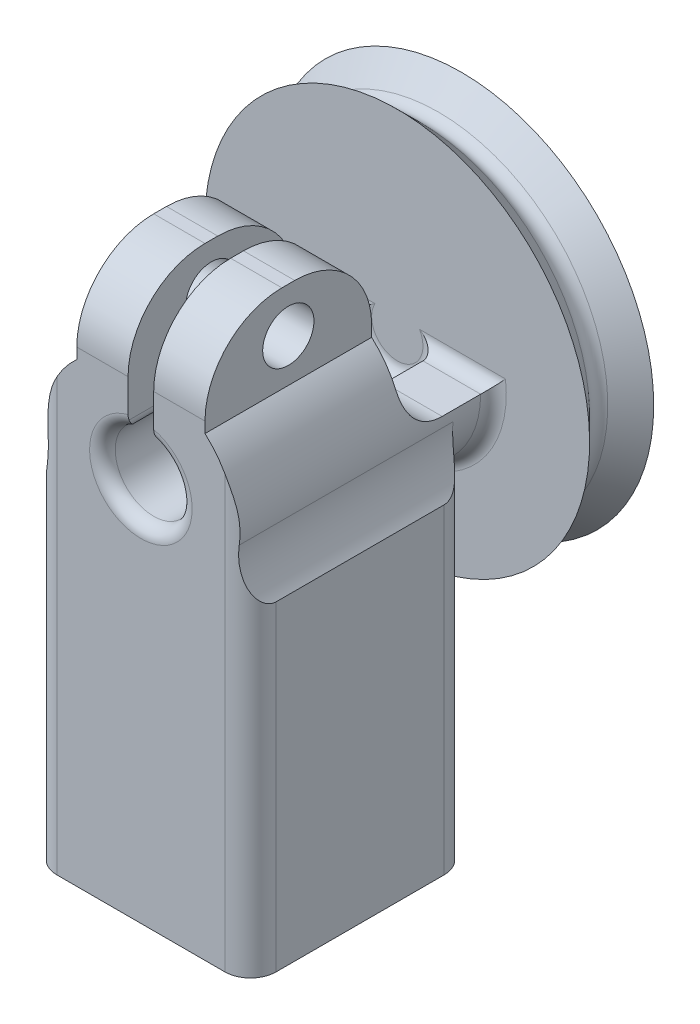
SolidWorks part; units mm, degrees
material "ABS PC"
ref_plane "Front Plane" through (0, 0, 0) normal (0, 0, 1) x (1, 0, 0)
ref_plane "Top Plane" through (0, 0, 0) normal (0, 1, 0) x (1, 0, 0)
ref_plane "Right Plane" through (0, 0, 0) normal (1, 0, 0) x (0, 0, -1)
sketch "Sketch1" plane through (0, 0, 0) normal (0, 0, 1) x (1, 0, 0)
  line L0 (-1, 7.433) -> (-1, 12.433)
  line L1 (-1, 12.433) -> (-5, 12.433)
  line L2 (-1, 2.8284) -> (-1, 7.433)
  line L3 (-5, 12.433) -> (-5, 5.5902)
  line L4 (1, 2.8284) -> (1, 7.433)
  line L5 (1, 7.433) -> (1, 12.433)
  line L6 (1, 12.433) -> (5, 12.433)
  line L7 (5, 12.433) -> (5, 5.5902)
  arc A0 (-5, 5.5902) -> (5, 5.5902) centre (0, 0) ccw
  arc A1 (-1, 2.8284) -> (1, 2.8284) centre (0, 0) ccw
  point P4 (0, 3)
  dimension "D1" = 6
  dimension "D2" = 15
  dimension "D3" = 5
  dimension "D4" = 5
  dimension "D5" = 4
  dimension "D6" = 4
extrude "Boss-Extrude1" add sketch "Sketch1" along normal blind 13
fillet "Fillet1" radius 1 3 edges at (0, -3, 13) (1, 2.8284, 6.5) (-1, 2.8284, 6.5)
fillet "Fillet2" radius 6 4 edges at (-3, 12.433, 0) (3, 12.433, 0) (3, 12.433, 13) (-3, 12.433, 13)
sketch "Sketch2" plane through (0, 0, 0) normal (0, 0, -1) x (-1, 0, 0)
  line L0 (-7.5, 0) -> (-3, 0)
  line L1 (3, 0) -> (7.5, 0)
  arc A0 (-7.5, 0) -> (7.5, 0) centre (0, 0) ccw
  arc A1 (-3, 0) -> (3, 0) centre (0, 0) ccw
extrude "Boss-Extrude2" add sketch "Sketch2" along normal blind 7
sketch "Sketch3" plane through (0, 0, 13) normal (0, 0, 1) x (1, 0, 0)
  line L1 (-8.55, -10) -> (8.55, -10)
  line L2 (-8.55, -10) -> (-8.55, -5)
  line L3 (-8.55, -5) -> (8.55, -5)
  line L4 (8.55, -10) -> (8.55, -5)
  line L5 (-8.55, -10) -> (8.55, -5) construction
  line L6 (-8.55, -5) -> (8.55, -10) construction
  arc A0 (-5, 5.5902) -> (5, 5.5902) centre (0, 0) ccw construction
  point P0 (0, -7.5)
  dimension "D1" = 17.1
  dimension "D2" = 5
extrude "Boss-Extrude3" add sketch "Sketch3" against normal blind 17.1
fillet "Fillet3" radius 6 2 edges at (5.5902, -5, 4.45) (-5.5902, -5, 4.45)
sketch "Sketch4" plane through (0, -10, 0) normal (0, -1, 0) x (1, 0, 0)
  line L4 (8.55, 13) -> (-8.55, 13)
  line L5 (-8.55, 13) -> (-8.55, -4.1)
  line L6 (-8.55, -4.1) -> (8.55, -4.1)
  line L7 (8.55, -4.1) -> (8.55, 13)
  line L8 (8.55, 13) -> (-8.55, 13)
  line L9 (-8.55, 13) -> (-8.55, -4.1)
  line L10 (-8.55, -4.1) -> (8.55, -4.1)
  line L11 (8.55, -4.1) -> (8.55, 13)
  dimension "D1" = 0
extrude "Boss-Extrude4" add sketch "Sketch4" along normal blind 20
fillet "Fillet4" radius 2 4 edges at (8.55, -17.5, -4.1) (8.55, -17.5, 13) (-8.55, -17.5, 13) (-8.55, -17.5, -4.1)
sketch "Sketch5" plane through (0, 0, 0) normal (1, 0, 0) x (0, 0, -1)
  line L0 (0, 0) -> (7, 0) construction
  line L1 (7, 0) -> (7, -15)
  line L2 (7, 0) -> (12, 0)
  line L3 (7, -15) -> (9.5, -12.5)
  line L4 (12, 0) -> (24.8319, 0) construction
  line L5 (9.5, -12.5) -> (12, -15)
  line L6 (12, -15) -> (12, 0)
  point P3 (9.5, 0)
  dimension "D1" = 15
  dimension "D2" = 15
  dimension "D3" = 12.5
  dimension "D4" = 2.5
  dimension "D5" = 2.5
revolve "Revolve1" add sketch "Sketch5" angle 360 about L0
fillet "Fillet6" radius 1 4 edges at (0, -3, -7) (-5.25, 0, -7) (5.25, 0, -7) (0, -7.5, -7)
fillet "Fillet7" radius 1 1 edges at (0, -12.5, -9.5)
sketch "Sketch6" plane through (-5, 0, 0) normal (-1, 0, 0) x (0, 0, 1)
  circle A0 centre (6.5, 8.9424) radius 2
  dimension "D1" = 4
extrude "Cut-Extrude1" cut sketch "Sketch6" against normal blind 14
fillet "Fillet8" radius 3 2 edges at (5.25, 0, 0) (-5.25, 0, 0)
